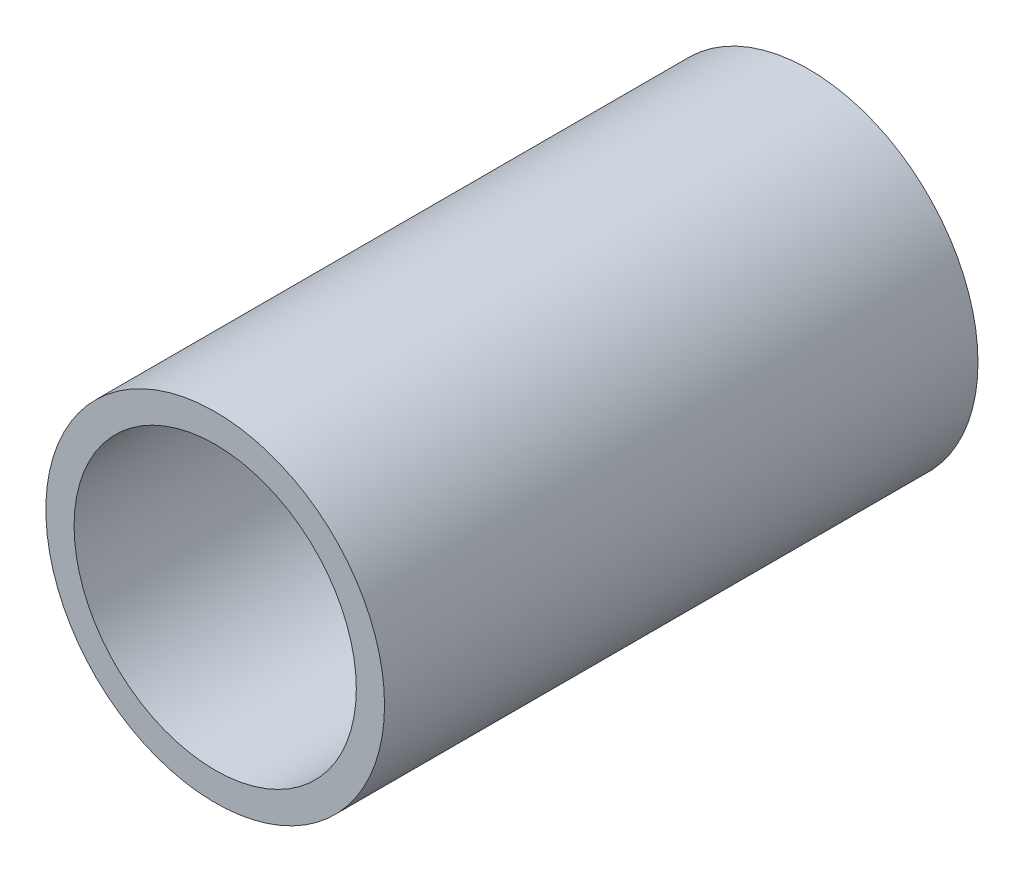
SolidWorks part; units mm, degrees
ref_plane "Front Plane" through (0, 0, 0) normal (0, 0, 1) x (1, 0, 0)
ref_plane "Top Plane" through (0, 0, 0) normal (0, 1, 0) x (1, 0, 0)
ref_plane "Right Plane" through (0, 0, 0) normal (1, 0, 0) x (0, 0, -1)
sketch "Sketch1" plane through (0, 0, 0) normal (0, 0, 1) x (1, 0, 0)
  circle A1 centre (0, 0) radius 9
  circle A2 centre (0, 0) radius 7.5
  dimension "D2" = 18
  dimension "D3" = 15
extrude "Boss-Extrude1" add sketch "Sketch1" against normal blind 27.5 contours A1 | A1 A2 region at (-8.7454, 0, 0)
extrude "Boss-Extrude2" add sketch "Sketch1<3>" along normal blind 4.04 contours A1 A2 region at (-8.7454, 0, 0)
sketch "Sketch1<3>" plane through (0, 0, 0) normal (0, 0, 1) x (1, 0, 0) same geometry as "Sketch1"
